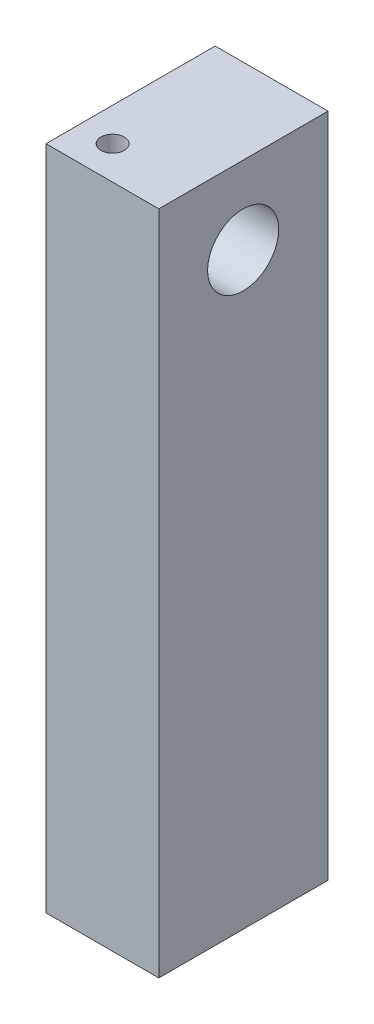
SolidWorks part; units mm, degrees
ref_plane "Front Plane" through (0, 0, 0) normal (0, 0, 1) x (1, 0, 0)
ref_plane "Top Plane" through (0, 0, 0) normal (0, 1, 0) x (1, 0, 0)
ref_plane "Right Plane" through (0, 0, 0) normal (1, 0, 0) x (0, 0, -1)
sketch "Sketch1" plane through (0, 0, 0) normal (0, 1, 0) x (1, 0, 0)
  line L1 (0, 0) -> (50.8, 0)
  line L2 (0, 0) -> (0, 76.2)
  line L3 (0, 76.2) -> (50.8, 76.2)
  line L4 (50.8, 0) -> (50.8, 76.2)
  dimension "D1" = 50.8
  dimension "D2" = 76.2
extrude "Boss-Extrude1" add sketch "Sketch1" along normal blind 300
sketch "Sketch2" plane through (50.8, 0, 0) normal (1, 0, 0) x (0, 0, -1)
  line L1 (0, 0) -> (38, 0)
  line L2 (0, 0) -> (0, 265)
  line L3 (0, 265) -> (38, 265)
  line L4 (38, 0) -> (38, 265)
  circle A0 centre (38, 265) radius 16
  dimension "D1" = 38
  dimension "D2" = 265
extrude "Cut-Extrude1" cut sketch "Sketch2" against normal blind 150 contours L4 A0 L3 | L3 A0 L4 region at (50.8, 258.2094, -31.2094) region at (50.8, 267.2635, -40.2635)
sketch "Sketch4" plane through (0, 300, 0) normal (0, 1, 0) x (1, 0, 0)
  line L5 (50.8, 0) -> (15, 0)
  line L6 (50.8, 0) -> (50.8, 15)
  line L7 (50.8, 15) -> (15, 15)
  line L8 (15, 0) -> (15, 15)
  circle A0 centre (15, 15) radius 5.25
  dimension "D1" = 35.8
  dimension "D2" = 15
extrude "Cut-Extrude3" cut sketch "Sketch4" against normal blind 50 contours A0
